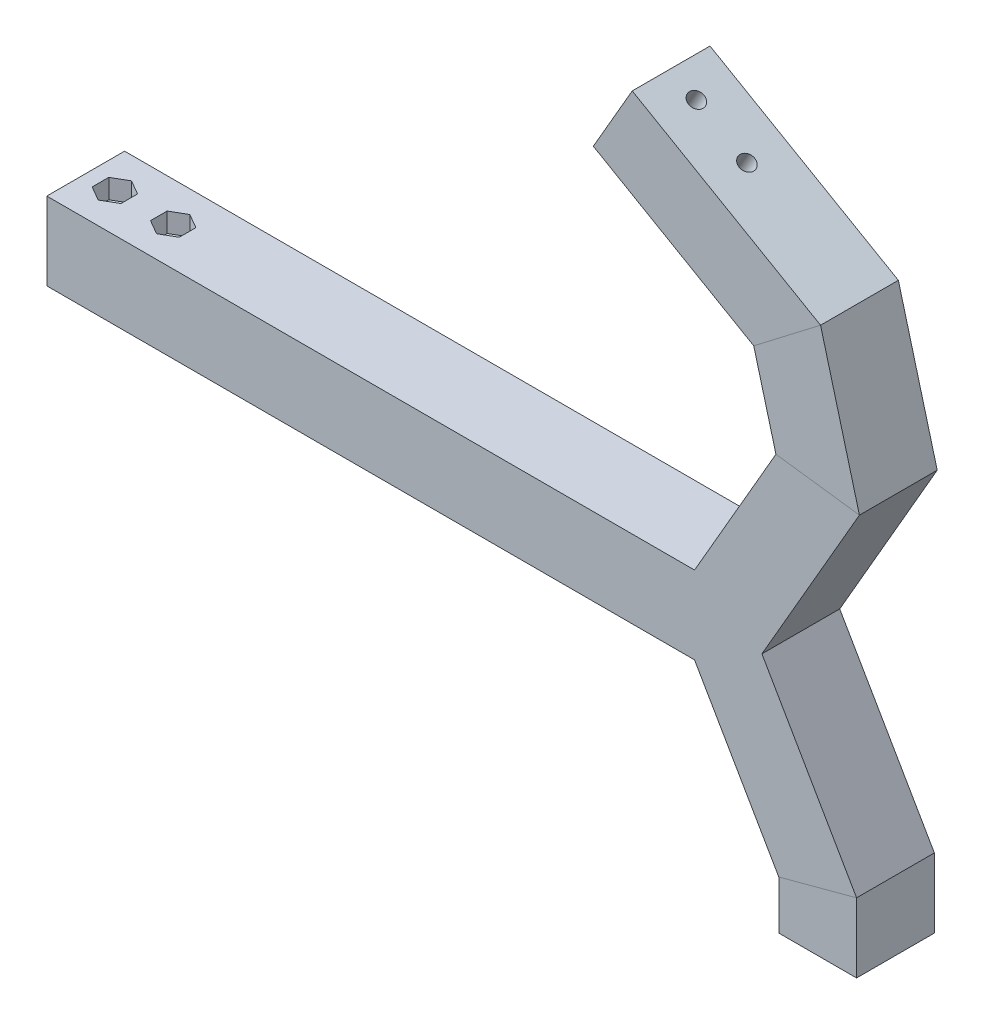
SolidWorks part; units mm, degrees
ref_plane "Front Plane" through (0, 0, 0) normal (0, 0, 1) x (1, 0, 0)
ref_plane "Top Plane" through (0, 0, 0) normal (0, 1, 0) x (1, 0, 0)
ref_plane "Right Plane" through (0, 0, 0) normal (1, 0, 0) x (0, 0, -1)
sketch "Sketch1" plane through (0, 0, 0) normal (0, 0, 1) x (1, 0, 0)
  line L0 (0, 0) -> (44.8288, -25.8819)
  line L1 (44.8288, -25.8819) -> (52.6768, -55.1712)
  line L2 (52.6768, -55.1712) -> (26.7949, -100)
  line L3 (0, 0) -> (26.7949, -100) construction
  line L4 (26.7949, -100) -> (-145.5051, -100)
  line L5 (26.7949, -100) -> (52.6768, -144.8288)
  line L6 (52.6768, -144.8288) -> (52.6768, -160)
  circle A0 centre (13.3975, -50) radius 36.6025 construction
  dimension "D1" = 135
  dimension "D2" = 30
  dimension "D3" = 100
  dimension "D4" = 172.3
  dimension "D5" = 120
  dimension "D6" = 60
ref_plane "Plane1" through (0, 0, 0) normal (-0.866, 0.5, 0) x (0, 0, 1)
sketch "Sketch2" plane through (0, 0, 0) normal (-0.866, 0.5, 0) x (0, 0, 1)
  line L1 (-10, -10) -> (10, -10)
  line L2 (-10, -10) -> (-10, 10)
  line L3 (-10, 10) -> (10, 10)
  line L4 (10, -10) -> (10, 10)
  line L5 (-10, -10) -> (10, 10) construction
  line L6 (-10, 10) -> (10, -10) construction
  point P0 (0, 0)
  dimension "D1" = 20
  dimension "D2" = 20
sweep "Sweep1" add profiles "Sketch2" path "Sketch1"
ref_plane "Plane2" through (-145.5051, -100, 0) normal (-1, 0, 0) x (0, 0, 1)
sketch "Sketch4" plane through (-145.5051, -100, 0) normal (-1, 0, 0) x (0, 0, 1)
  line L1 (-10, -10) -> (10, -10)
  line L2 (-10, -10) -> (-10, 10)
  line L3 (-10, 10) -> (10, 10)
  line L4 (10, -10) -> (10, 10)
  line L5 (-10, -10) -> (10, 10) construction
  line L6 (-10, 10) -> (10, -10) construction
  point P0 (0, 0)
  dimension "D1" = 20
  dimension "D2" = 20
sweep "Sweep3" add profiles "Sketch4" path "Sketch1<5>"
sketch "Sketch1<5>" plane through (0, 0, 0) normal (0, 0, 1) x (1, 0, 0) same geometry as "Sketch1"
sketch "Sketch5" plane through (5, 8.6603, 0) normal (0.5, 0.866, 0) x (0.866, -0.5, 0)
  line L0 (0, 0) -> (55.9059, 0) construction
  line L1 (55.9059, 10) -> (55.9059, -10) construction
  line L2 (0, -10) -> (0, 10) construction
  line L3 (7.5, 4.2724) -> (3.8, 2.1362)
  line L4 (3.8, 2.1362) -> (3.8, -2.1362)
  line L5 (3.8, -2.1362) -> (7.5, -4.2724)
  line L6 (7.5, -4.2724) -> (11.2, -2.1362)
  line L7 (11.2, -2.1362) -> (11.2, 2.1362)
  line L8 (11.2, 2.1362) -> (7.5, 4.2724)
  line L9 (22.5, 4.2724) -> (18.8, 2.1362)
  line L10 (18.8, 2.1362) -> (18.8, -2.1362)
  line L11 (18.8, -2.1362) -> (22.5, -4.2724)
  line L12 (22.5, -4.2724) -> (26.2, -2.1362)
  line L13 (26.2, -2.1362) -> (26.2, 2.1362)
  line L14 (26.2, 2.1362) -> (22.5, 4.2724)
  circle A0 centre (7.5, 0) radius 3.7 construction
  circle A1 centre (22.5, 0) radius 3.7 construction
  circle A2 centre (7.5, 0) radius 2
  circle A3 centre (22.5, 0) radius 2
  dimension "D4" = 4
  dimension "D1" = 7.4
  dimension "D2" = 7.5
  dimension "D3" = 15
extrude "Cut-Extrude1" cut sketch "Sketch5" against normal up to next contours A2 | A3 region at (11.4952, 4.9103, 0) region at (24.4856, -2.5897, 0)
extrude "Cut-Extrude2" cut sketch "Sketch5<3>" along normal blind 5 from surface contours L7 L8 L3 L4 L5 L6 A2 | L13 L14 L9 L10 L11 L12 A3 region at (13.0484, 4.0135, -3.1064) region at (26.0388, -3.4865, -3.1064) starting at face at (12.7535, -18.9103, 0)
sketch "Sketch5<3>" plane through (5, 8.6603, 0) normal (0.5, 0.866, 0) x (0.866, -0.5, 0) same geometry as "Sketch5"
sketch "Sketch6" plane through (0, -90, -90) normal (0, 1, 0) x (1, 0, 0)
  line L0 (-145.5051, -90) -> (-5, -90) construction
  line L3 (-138.0051, -85.7276) -> (-141.7051, -87.8638)
  line L4 (-141.7051, -87.8638) -> (-141.7051, -92.1362)
  line L5 (-141.7051, -92.1362) -> (-138.0051, -94.2724)
  line L6 (-138.0051, -94.2724) -> (-134.3051, -92.1362)
  line L7 (-134.3051, -92.1362) -> (-134.3051, -87.8638)
  line L8 (-134.3051, -87.8638) -> (-138.0051, -85.7276)
  line L9 (-123.0051, -85.7276) -> (-126.7051, -87.8638)
  line L10 (-126.7051, -87.8638) -> (-126.7051, -92.1362)
  line L11 (-126.7051, -92.1362) -> (-123.0051, -94.2724)
  line L12 (-123.0051, -94.2724) -> (-119.3051, -92.1362)
  line L13 (-119.3051, -92.1362) -> (-119.3051, -87.8638)
  line L14 (-119.3051, -87.8638) -> (-123.0051, -85.7276)
  line L15 (-145.5051, -100) -> (-145.5051, -80) construction
  line L16 (-5, -80) -> (-5, -100) construction
  circle A0 centre (-138.0051, -90) radius 3.7 construction
  circle A1 centre (-123.0051, -90) radius 3.7 construction
  circle A2 centre (-138.0051, -90) radius 2
  circle A3 centre (-123.0051, -90) radius 2
  dimension "D4" = 4
  dimension "D1" = 7.4
  dimension "D2" = 7.5
  dimension "D3" = 15
extrude "Cut-Extrude3" cut sketch "Sketch6" against normal up to next contours A2 | A3 region at (-138.0051, -90, 0) region at (-123.0051, -90, 0)
extrude "Cut-Extrude4" cut sketch "Sketch6<5>" against normal blind 5 contours L7 L8 L3 L4 L5 L6 A2 | L13 L14 L9 L10 L11 L12 A3 region at (-136.2116, -90, -3.1064) region at (-121.2116, -90, -3.1064)
sketch "Sketch6<5>" plane through (0, -90, -90) normal (0, 1, 0) x (1, 0, 0) same geometry as "Sketch6"
